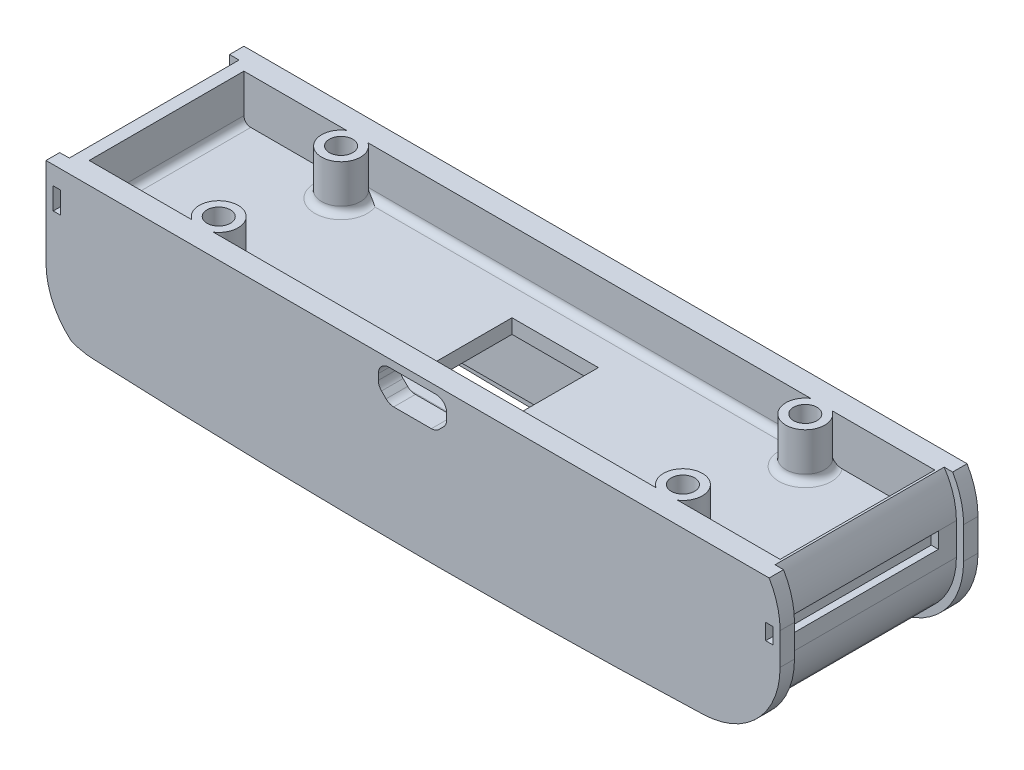
SolidWorks part; units mm, degrees
material "ABS"
ref_plane "Front" through (0, 0, 0) normal (0, 0, 1) x (1, 0, 0)
ref_plane "Top" through (0, 0, 0) normal (0, 1, 0) x (1, 0, 0)
ref_plane "Right" through (0, 0, 0) normal (1, 0, 0) x (0, 0, -1)
sketch "草图1" plane through (0, 0, 0) normal (0, 1, 0) x (1, 0, 0)
  line L0 (-48, 10.75) -> (-50, 10.75) construction
  line L6 (-48, 9.7892) -> (-48, -9.7108)
  line L12 (48, 9.7892) -> (48, -9.7108)
  line L13 (-48, 10.75) -> (48, -10.75) construction
  line L14 (-48, -10.75) -> (43.5349, 9.75) construction
  line L15 (-50, 12.75) -> (50, 12.75)
  line L16 (-50, 12.75) -> (-50, -12.75)
  line L17 (-50, -12.75) -> (50, -12.75)
  line L18 (50, 12.75) -> (50, -12.75)
  line L19 (-50, 12.75) -> (50, -12.75) construction
  line L20 (-50, -12.75) -> (-38.2259, -9.7476) construction
  line L21 (-48, 10.75) -> (-48, 12.75) construction
  line L24 (-48, 9.7892) -> (-48, 10.75)
  line L25 (-48, 10.75) -> (45.2523, 10.75)
  line L26 (45.2523, -13.75) -> (45.2523, 13.75) construction
  line L27 (48, 10.75) -> (-48, 10.75) construction
  line L29 (-48, -9.7108) -> (-48, -10.75)
  line L30 (-48, -10.75) -> (48, -10.75)
  line L31 (48, -10.75) -> (48, -9.7108)
  line L32 (0, 0) -> (42.1569, 10.75) construction
  line L33 (45.2523, 10.75) -> (48, 10.75)
  line L34 (48, 10.75) -> (48, 9.7892)
  point P0 (0, 0)
  point P6 (0, 0)
  dimension "D3" = 96
extrude "凸台-拉伸1" add sketch "草图1" along normal blind 13.2
sketch "草图2" plane through (0, 13.2, 0) normal (0, 1, 0) x (1, 0, 0)
  line L1 (-48, 10.75) -> (48, 10.75)
  line L2 (-48, 10.75) -> (-48, -10.75)
  line L3 (-48, -10.75) -> (48, -10.75)
  line L4 (48, 10.75) -> (48, -10.75)
  line L5 (-48, 10.75) -> (48, -10.75) construction
  line L6 (-48, -10.75) -> (48, 10.75) construction
  line L7 (-6, 6) -> (6, 6)
  line L8 (-6, 6) -> (-6, -6)
  line L9 (-6, -6) -> (6, -6)
  line L10 (6, 6) -> (6, -6)
  line L11 (-6, 6) -> (6, -6) construction
  line L12 (-6, -6) -> (6, 6) construction
  point P0 (0, 0)
  point P7 (0, 0)
  point P8 (0, 0)
  dimension "D1" = 12
extrude "凸台-拉伸2" add sketch "草图2" against normal blind 2
sketch "草图3" plane through (0, 13.2, 0) normal (0, 1, 0) x (1, 0, 0)
  line L0 (0, 0) -> (-50, 0) construction
  line L1 (-50, 12.75) -> (-50, -12.75) construction
  line L2 (-50, -12.75) -> (-50, 12.75)
  line L3 (-50, 12.75) -> (50, 12.75)
  line L4 (50, 12.75) -> (50, -0.0404)
  line L5 (50, -12.75) -> (50, 12.75) construction
  line L7 (48, 0.0137) -> (48, 10.75)
  line L8 (48, 10.75) -> (-48, 10.75)
  line L9 (-48, 10.75) -> (-48, -10.75)
  line L10 (48, -10.75) -> (-48, -10.75)
  line L11 (48, 0.0137) -> (48, -10.75)
  line L13 (50, -12.75) -> (50, -0.0404)
  line L14 (-50, -12.75) -> (50, -12.75)
  line L15 (48, 10.75) -> (-48, 10.75) construction
  line L16 (-48, 10.75) -> (-48, -10.75) construction
  line L17 (48, -10.75) -> (48, 10.75) construction
  point P17 (-48, 0)
extrude "凸台-拉伸3" add sketch "草图3" along normal blind 6.3
sketch "草图6" plane through (0, 19.5, 0) normal (0, 1, 0) x (1, 0, 0)
  line L0 (50, 0) -> (0, 0) construction
  line L1 (32.25, 8.5) -> (-39.5985, 8.5) construction
  line L2 (32.25, -8.5) -> (-29.1938, -8.5) construction
  line L4 (50, -12.75) -> (50, 12.75) construction
  circle A0 centre (32.25, 8.5) radius 2.7
  circle A1 centre (32.25, -8.5) radius 2.7
  circle A2 centre (-32.25, -8.5) radius 2.7
  circle A3 centre (-32.25, 8.5) radius 2.7
  dimension "D1" = 5.4
  dimension "D2" = 32.25
  dimension "D3" = 17
  dimension "D4" = 32.25
extrude "凸台-拉伸4" add sketch "草图6" against normal up to next
sketch "草图7" plane through (0, 19.5, 0) normal (0, 1, 0) x (1, 0, 0)
  line L0 (0, 12.75) -> (0, 0) construction
  line L2 (0, 0) -> (50, 0) construction
  line L4 (50, 12.75) -> (-50, 12.75) construction
  line L5 (50, -12.75) -> (50, 12.75) construction
  circle A0 centre (32.25, 8.5) radius 1.625
  circle A1 centre (32.25, -8.5) radius 1.625
  circle A2 centre (-32.25, -8.5) radius 1.625
  circle A3 centre (-32.25, 8.5) radius 1.625
  dimension "D1" = 3.25
  dimension "D2" = 32.25
  dimension "D3" = 32.25
extrude "切除-拉伸3" cut sketch "草图7" against normal blind 5.5
sketch "草图10" plane through (0, 11.2, 0) normal (0, -1, 0) x (1, 0, 0)
  line L1 (-7.1, 7.1) -> (7.1, 7.1)
  line L2 (-7.1, 7.1) -> (-7.1, -7.1)
  line L3 (-7.1, -7.1) -> (7.1, -7.1)
  line L4 (7.1, 7.1) -> (7.1, -7.1)
  line L5 (-7.1, 7.1) -> (7.1, -7.1) construction
  line L6 (-7.1, -7.1) -> (7.1, 7.1) construction
  line L7 (-7.9, 7.9) -> (7.9, 7.9)
  line L8 (-7.9, 7.9) -> (-7.9, -7.9)
  line L9 (-7.9, -7.9) -> (7.9, -7.9)
  line L10 (7.9, 7.9) -> (7.9, -7.9)
  line L11 (-7.9, 7.9) -> (7.9, -7.9) construction
  line L12 (-7.9, -7.9) -> (7.9, 7.9) construction
  point P11 (0, 0)
  point P13 (0, 0)
  dimension "D1" = 14.2
  dimension "D2" = 0.8
extrude "凸台-拉伸5" add sketch "草图10" along normal blind 0.8 contours L10 L7 L8 L9 L1 L4 L3 L2 region at (0, 11.2, 7.6766)
sketch "草图11" plane through (0, 0, 12.75) normal (0, 0, 1) x (1, 0, 0)
  line L0 (0, 0) -> (0, 19.5) construction
  line L1 (-4, 17.65) -> (4, 17.65)
  line L2 (4, 17.65) -> (4, 15.8)
  line L3 (4, 15.8) -> (3, 14.8)
  line L4 (3, 14.8) -> (-3, 14.8)
  line L5 (-4, 15.8) -> (-3, 14.8)
  line L6 (-4, 17.65) -> (-4, 15.8)
  line L7 (-50, 19.5) -> (50, 19.5) construction
  line L8 (-30.7575, 13.2) -> (30.7575, 13.2) construction
  point P7 (0, 14.8)
  point P9 (0, 17.65)
  dimension "D1" = 8
  dimension "D2" = 135
  dimension "D3" = 1
  dimension "D4" = 1.6
  dimension "D5" = 2.85
extrude "切除-拉伸5" cut sketch "草图11" against normal blind 3
fillet "圆角6" radius 0.5 6 edges at (4, 15.8, 11.75) (3, 14.8, 11.75) (-3, 14.8, 11.75) (-4, 15.8, 11.75) (-4, 17.65, 11.75) (4, 17.65, 11.75)
fillet "圆角3" radius 0.95 8 edges at (0, 13.2, -10.75) (32.25, 13.2, -5.8) (32.25, 13.2, 5.8) (0, 13.2, 10.75) (-32.25, 13.2, 5.8) (-48, 13.2, 0) (-32.25, 13.2, -5.8) (48, 13.2, 0)
fillet "圆角1" radius 2 4 edges at (50, 9.75, -12.75) (-50, 9.75, 12.75) (50, 9.75, 12.75) (-50, 9.75, -12.75)
ref_plane "基准面3" through (0, 0, -10.75) normal (0, 0, -1) x (-1, 0, 0)
sketch "草图23" plane through (0, 0, -10.75) normal (0, 0, -1) x (-1, 0, 0)
  line L0 (-50, 19.5) -> (-50, -0.5)
  line L5 (-48, 19.5) -> (-50, 19.5) construction
  line L6 (-50, -0.5) -> (51, -0.5)
  line L7 (51, -0.5) -> (51, 19.5)
  line L8 (51, 19.5) -> (-50, 19.5)
sketch "草图18" plane through (0, 19.5, 0) normal (0, 1, 0) x (1, 0, 0)
  line L0 (-48, -12.75) -> (-53, -12.75)
  line L1 (-53, 26) -> (-53, -26) construction
  line L2 (-53, -12.75) -> (-53, -11.8645)
  line L6 (-37.0111, -11.75) -> (-37.0111, -12.75)
  line L7 (-48, -12.75) -> (48, -12.75) construction
  line L8 (-37.0111, -12.75) -> (-48, -12.75)
  line L9 (-37.0111, 11.75) -> (-37.0111, 12.75)
  line L11 (48, 12.75) -> (-48, 12.75) construction
  line L12 (-37.0111, 12.75) -> (-53, 12.75)
  line L13 (-53, 12.75) -> (-53, 11.75)
  line L15 (-53, -11.8645) -> (-37.0111, -11.75)
  line L16 (-53, 11.75) -> (-37.0111, 11.75)
extrude "凸台-拉伸7" add sketch "草图18" against normal blind 20
sketch "草图19" plane through (-53, 0, 0) normal (-1, 0, 0) x (0, 0, 1)
  line L0 (11.8736, -0.5079) -> (26.8736, -0.5079)
  line L1 (26.8736, -0.5079) -> (26.8736, 19.4921)
  line L2 (26.8736, 19.4921) -> (11.8736, 19.4921)
  line L3 (11.8736, 19.4921) -> (11.8736, -0.5079)
  line L4 (-11.75, -0.5) -> (-26.75, -0.5)
  line L5 (-12.75, -0.5) -> (-11.75, -0.5) construction
  line L6 (-11.75, -0.5) -> (-11.75, 19.5) construction
  line L7 (-26.75, -0.5) -> (-26.75, 19.5)
  line L8 (-26.75, 19.5) -> (-11.75, 19.5)
  line L9 (-11.75, 19.5) -> (-11.75, -0.5)
extrude "凸台-拉伸8" add sketch "草图19" against normal blind 2
sketch "草图20" plane through (-53, 0, 0) normal (-1, 0, 0) x (0, 0, 1)
  line L0 (0, 13.9) -> (0, -6.4084) construction
  line L1 (0, 54.2543) -> (0, -9.2543) construction
  line L2 (11.8736, -0.5079) -> (26.8736, -0.5079) construction
  circle A0 centre (20, 11.9921) radius 1.55
  circle A1 centre (-20, 11.9921) radius 1.55
  dimension "D1" = 40
  dimension "D2" = 12.5
extrude "切除-拉伸8" cut sketch "草图20" against normal blind 2
sketch "草图21" plane through (0, 0, -11.75) normal (0, 0, 1) x (1, 0, 0)
  line L1 (-50, 11.869) -> (-50, 16.9603)
  line L5 (-57.0725, 46.2563) -> (-50, 11.869)
  line L6 (-33.7407, 53.4984) -> (-57.0725, 46.2563)
  line L7 (-49.0355, 21.245) -> (-33.7407, 53.4984)
  arc A1 (-49.0355, 21.245) -> (-50, 16.9603) centre (-40, 16.9603) ccw
sketch "草图22" plane through (0, 0, 12.75) normal (0, 0, 1) x (1, 0, 0)
  line L0 (45.2523, 22.4304) -> (34.9699, 28.7768)
  line L1 (-31.6973, 69.925) -> (45.1395, 22.5) construction
  line L2 (50, 13.9208) -> (50, 4.3791)
  line L3 (50, 4.3791) -> (55.1917, 10.9989)
  line L4 (55.1917, 10.9989) -> (47.2062, 26.2201)
  line L5 (47.2062, 26.2201) -> (34.9699, 28.7768)
  arc A0 (45.2523, 22.4304) -> (50, 13.9208) centre (40, 13.9208) cw
  point P8 (50, 19.5)
  dimension "D1" = 10
extrude "凸台-拉伸13" add sketch "草图23" along normal blind 3 contours L0 L6 L7 L8
sketch "草图24" plane through (0, 0, 10.75) normal (0, 0, -1) x (-1, 0, 0)
  line L1 (-50, 19.5) -> (51, 19.5)
  line L2 (-50, 19.5) -> (-50, -0.5)
  line L3 (-50, -0.5) -> (51, -0.5)
  line L4 (51, 19.5) -> (51, -0.5)
extrude "凸台-拉伸15" add sketch "草图24" against normal blind 3
sketch "草图25" plane through (0, 0, -11.75) normal (0, 0, 1) x (1, 0, 0)
  line L6 (-38.7381, -0.4978) -> (-51.3208, -1.77)
  line L7 (-51.4889, 1.3597) -> (-50, 19.5)
  line L8 (-51.3208, -1.77) -> (-51.4889, 1.3597)
  line L9 (-50, 19.5) -> (-50, 9.5596)
  line L11 (50, 19.5) -> (55.4643, -8.4655)
  line L12 (50, 19.5) -> (50, 9.5765)
  arc A3 (-40.4019, -0.4323) -> (-50, 9.5596) centre (-40, 9.5596) cw
  arc A4 (50, 9.5765) -> (40.4061, -0.4153) centre (40, 9.5765) cw
  arc A5 (-40.4019, -0.4323) -> (-38.7381, -0.4978) centre (-0.2081, 998.7596) ccw
extrude "切除-拉伸13" cut sketch "草图22" against normal mid plane 80
extrude "切除-拉伸14" cut sketch "草图21" along normal up to surface (23.4766 mm away) up to face at (-52, 9.5, 11.8574)
extrude "切除-拉伸15" cut sketch "草图25" along normal up to surface (23.5243 mm away) contours L6 L8 L7 L9 A3 A5 up to face at (-51.1077, 11.9387, 11.851)
sketch "草图26" plane through (0, 0, -11.75) normal (0, 0, 1) x (1, 0, 0)
  line L0 (-51.0483, 18.4275) -> (-51.8061, 12.9844)
  line L1 (-51.8061, 12.9844) -> (-50.9317, 5.1015)
  line L2 (-50.9317, 5.1015) -> (-50.2088, 15.1871)
  line L3 (-50.2088, 15.1871) -> (-51.0483, 18.4275)
extrude "切除-拉伸16" cut sketch "草图26" along normal up to surface (23.5997 mm away) up to face at (-50.8159, 12.6978, 11.8489)
sketch "草图27" plane through (0, 0, -13.75) normal (0, 0, -1) x (-1, 0, 0)
  line L0 (-50, 9.8308) -> (-50, 9.5)
  line L1 (-50, 13.9208) -> (-50, -0.5) construction
  line L2 (-40, -0.5) -> (-39.276, -0.5)
  line L3 (-50, -0.5) -> (51, -0.5) construction
  line L4 (-39.276, -0.5) -> (-53.1302, -4.8854)
  line L5 (-53.1302, -4.8854) -> (-50, 9.8308)
  arc A0 (-50, 9.5) -> (-40, -0.5) centre (-40, 9.5) ccw
  point P11 (-50, -0.5)
  dimension "D1" = 10
extrude "切除-拉伸17" cut sketch "草图27" against normal up to surface (27.5 mm away) up to face at (-0.7142, 11.9233, 13.75)
sketch "草图29" plane through (0, 0, 13.75) normal (0, 0, 1) x (1, 0, 0)
  line L0 (51, 9.5) -> (51, 13.9208)
  line L1 (48.2989, 19.5) -> (49.4801, 19.5)
  line L3 (48.2989, 19.5) -> (4.9263, 6.9163)
  line L4 (4.9263, 6.9163) -> (-47.4572, -0.5)
  line L5 (40, -0.5) -> (-51, -0.5) construction
  arc A2 (51, 13.9208) -> (49.4801, 19.5) centre (40, 13.9208) ccw
  arc A4 (40.3393, -1.4948) -> (-44.3288, -1.12) centre (2.6099, 1039.0132) cw
  arc A5 (-47.4572, -0.5) -> (-44.3288, -1.12) centre (-43.9952, 8.7656) ccw
  arc A7 (40.3393, -1.4948) -> (51, 9.5) centre (40, 9.5) ccw
extrude "凸台-拉伸16" add sketch "草图29" against normal blind 2
sketch "草图30" plane through (0, 0, -13.75) normal (0, 0, -1) x (-1, 0, 0)
  line L5 (-4.9263, 6.9163) -> (47.4572, -0.5)
  line L6 (-48.2989, 19.5) -> (-4.9263, 6.9163)
  line L7 (-48.2989, 19.5) -> (-49.4801, 19.5)
  line L8 (-51, 9.5) -> (-51, 13.9208)
  arc A4 (-40.3393, -1.4948) -> (-51, 9.5) centre (-40, 9.5) cw
  arc A5 (47.4572, -0.5) -> (44.3288, -1.12) centre (43.9952, 8.7656) cw
  arc A6 (-40.3393, -1.4948) -> (44.3288, -1.12) centre (-2.6099, 1039.0132) ccw
  arc A7 (-51, 13.9208) -> (-49.4801, 19.5) centre (-40, 13.9208) cw
extrude "凸台-拉伸17" add sketch "草图30" against normal up to surface (2 mm away) up to face at (-46.958, 7.7086, -11.75)
sketch "草图32" plane through (0, 0, 13.75) normal (0, 0, 1) x (1, 0, 0)
  line L12 (-4.8199, 16.95) -> (-4.8199, 16.1329)
  line L13 (-4.3806, 15.0722) -> (-3.7477, 14.4394)
  line L14 (-2.6871, 14) -> (2.5471, 14)
  line L15 (3.6078, 14.4394) -> (4.2406, 15.0722)
  line L16 (4.68, 16.1329) -> (4.68, 16.95)
  line L17 (3.18, 18.45) -> (-3.3199, 18.45)
  line L18 (-4.8199, 16.95) -> (-4.8199, 16.1329)
  line L19 (-4.3806, 15.0722) -> (-3.7477, 14.4394)
  line L20 (-2.6871, 14) -> (2.5471, 14)
  line L21 (3.6078, 14.4394) -> (4.2406, 15.0722)
  line L22 (4.68, 16.1329) -> (4.68, 16.95)
  line L23 (3.18, 18.45) -> (-3.3199, 18.45)
  arc A12 (-3.3199, 18.45) -> (-4.8199, 16.95) centre (-3.3199, 16.95) ccw
  arc A13 (-4.8199, 16.1329) -> (-4.3806, 15.0722) centre (-3.3199, 16.1329) ccw
  arc A14 (-3.7477, 14.4394) -> (-2.6871, 14) centre (-2.6871, 15.5) ccw
  arc A15 (2.5471, 14) -> (3.6078, 14.4394) centre (2.5471, 15.5) ccw
  arc A16 (4.2406, 15.0722) -> (4.68, 16.1329) centre (3.18, 16.1329) ccw
  arc A17 (4.68, 16.95) -> (3.18, 18.45) centre (3.18, 16.95) ccw
  arc A18 (-3.3199, 18.45) -> (-4.8199, 16.95) centre (-3.3199, 16.95) ccw
  arc A19 (-4.8199, 16.1329) -> (-4.3806, 15.0722) centre (-3.3199, 16.1329) ccw
  arc A20 (-3.7477, 14.4394) -> (-2.6871, 14) centre (-2.6871, 15.5) ccw
  arc A21 (2.5471, 14) -> (3.6078, 14.4394) centre (2.5471, 15.5) ccw
  arc A22 (4.2406, 15.0722) -> (4.68, 16.1329) centre (3.18, 16.1329) ccw
  arc A23 (4.68, 16.95) -> (3.18, 18.45) centre (3.18, 16.95) ccw
  dimension "D1" = 1
extrude "切除-拉伸18" cut sketch "草图32" against normal blind 10
sketch "草图33" plane through (50, 0, 0) normal (1, 0, 0) x (0, 0, -1)
  line L1 (9.25, 13.9208) -> (-9.25, 13.9208)
  line L3 (9.25, 11.7104) -> (-9.25, 11.7104)
  line L5 (9.25, 13.9208) -> (9.25, 11.7104)
  line L6 (-9.25, 13.9208) -> (-9.25, 11.7104)
extrude "切除-拉伸19" cut sketch "草图33" against normal blind 1
sketch "草图34" plane through (0, 0, 13.75) normal (0, 0, 1) x (1, 0, 0)
  line L0 (49, 13.9208) -> (49, 11.7104) construction
  line L1 (49, 13.9208) -> (50, 13.9208) construction
  line L2 (50, 9.5) -> (50, 13.9208) construction
  line L3 (49, 11.7104) -> (50, 11.7104) construction
  line L4 (49, 13.9208) -> (49, 11.7104)
  line L5 (49, 13.9208) -> (50, 13.9208)
  line L6 (50, 11.7104) -> (50, 13.9208)
  line L7 (49, 11.7104) -> (50, 11.7104)
extrude "切除-拉伸20" cut sketch "草图34" against normal blind 10 contours L6 L5 L4 L7
sketch "草图35" plane through (-50, 0, 0) normal (-1, 0, 0) x (0, 0, 1)
  line L1 (-9.25, 13.9208) -> (-9.25, 16.9603)
  line L2 (11.843, 16.9603) -> (-9.25, 16.9603)
  line L3 (11.843, 16.9603) -> (11.843, 16.95)
  line L4 (11.843, 13.9208) -> (-9.25, 13.9208)
  line L6 (11.843, 13.9208) -> (13.75, 13.9208)
  line L8 (11.843, 16.95) -> (13.75, 16.95)
  line L9 (13.75, 13.9208) -> (13.75, 16.95)
extrude "切除-拉伸21" cut sketch "草图35" against normal blind 1
sketch "草图38" plane through (-51, 0, 0) normal (1, 0, 0) x (0, 0, -1)
  line L1 (-28.1477, 20.2918) -> (28.6102, 20.2918)
  line L2 (-28.1477, 20.2918) -> (-28.1477, -1.8433)
  line L3 (-28.1477, -1.8433) -> (28.6102, -1.8433)
  line L4 (28.6102, 20.2918) -> (28.6102, -1.8433)
extrude "切除-拉伸25" cut sketch "草图38" against normal blind 10
fillet "圆角7" radius 10 2 edges at (-51, -0.5, -12.75) (-51, -0.5, 12.8001)
sketch "草图41" plane through (0, 11.2, 0) normal (0, -1, 0) x (1, 0, 0)
  line L1 (-48, 10.75) -> (-38.7596, 10.75)
  line L2 (-48, 10.75) -> (-48, -10.75)
  line L3 (-48, -10.75) -> (-38.7596, -10.75)
  line L4 (-38.7596, 10.75) -> (-38.7596, -10.75)
  line L5 (48, 10.75) -> (40, 10.75)
  line L6 (48, 10.75) -> (48, -10.75)
  line L7 (48, -10.75) -> (40, -10.75)
  line L8 (40, 10.75) -> (40, -10.75)
extrude "凸台-拉伸19" add sketch "草图41" along normal blind 11.69
fillet "圆角8" radius 10 2 edges at (48, -0.49, 0) (-48, -0.49, 0)
